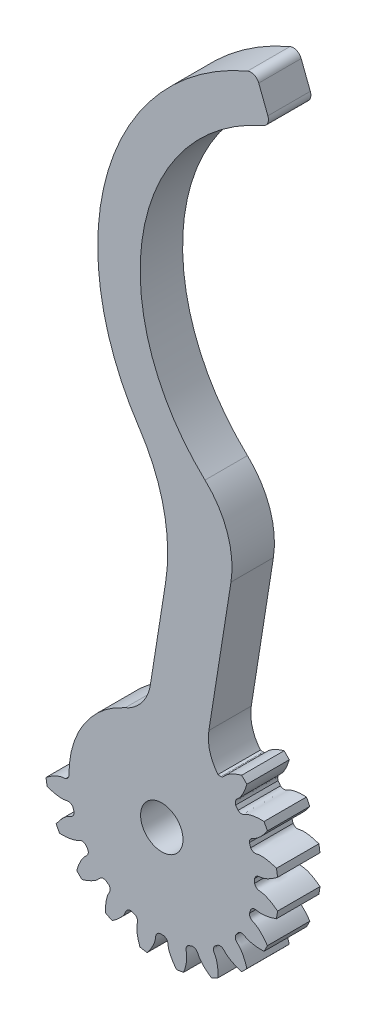
SolidWorks part; units mm, degrees
material "聚脂树脂"
ref_plane "前视基准面" through (0, 0, 0) normal (0, 0, 1) x (1, 0, 0)
ref_plane "上视基准面" through (0, 0, 0) normal (0, 1, 0) x (1, 0, 0)
ref_plane "右视基准面" through (0, 0, 0) normal (1, 0, 0) x (0, 0, -1)
other "Configuration Table"
sketch "草图1" plane through (0, 0, 0) normal (0, 0, 1) x (1, 0, 0)
  circle A0 centre (0, 0) radius 13.75
extrude "凸台-拉伸1" add sketch "草图1" along normal blind 5
ref_axis "基准轴1" through (0, 0, -1.5) along (0, 0, 1)
sketch "草图2" plane through (0, 0, 0) normal (0, 0, 1) x (1, 0, 0)
  line L0 (0, 0) -> (0, 13.75) construction
  circle A0 centre (0, 0) radius 13.75 construction
  arc A1 (0.2416, 10.9348) -> (-0.2416, 10.9348) centre (0, 0) ccw
  arc A2 (3.9764, 15.6228) -> (-3.9764, 15.6228) centre (0, 0) ccw
  spline S0 degree 3 poles (0.2416, 10.9348) (0.764, 11.1168) (0.6964, 11.4839) (0.7661, 11.8375) (0.7736, 11.8719) (0.7829, 11.9108) (0.7941, 11.954) (0.8075, 12.0015) (0.8231, 12.0532) (0.8413, 12.1091) (0.8621, 12.169) (0.8857, 12.2329) (0.9123, 12.3007) (0.9421, 12.3723) (0.9752, 12.4476) (1.0117, 12.5264) (1.0519, 12.6088) (1.0959, 12.6945) (1.1438, 12.7834) (1.1957, 12.8755) (1.2519, 12.9705) (1.3125, 13.0684) (1.3775, 13.1691) (1.4472, 13.2723) (1.5216, 13.3779) (1.601, 13.4858) (1.6853, 13.5958) (1.7747, 13.7078) (1.8694, 13.8216) (1.9693, 13.937) (2.0748, 14.0539) (2.1857, 14.1721) (2.3023, 14.2914) (2.4246, 14.4116) (2.5527, 14.5326) (2.6866, 14.6542) (2.8265, 14.7761) (2.9725, 14.8983) (3.1245, 15.0204) (3.2826, 15.1424) (3.4469, 15.2639) (3.6768, 15.427) (3.8549, 15.5454) (3.9764, 15.6228) knots 0 0 0 0 0.165916 0.170906 0.176664 0.183189 0.190482 0.198542 0.207371 0.216967 0.22733 0.238462 0.250361 0.263027 0.276462 0.290664 0.305634 0.321371 0.337876 0.355149 0.37319 0.391998 0.411574 0.431917 0.453028 0.474907 0.497554 0.520968 0.54515 0.570099 0.595817 0.622302 0.649554 0.677575 0.706363 0.735918 0.766242 0.797333 0.829191 0.861818 0.895212 0.929373 1 1 1 1
  spline S1 degree 3 poles (-0.2416, 10.9348) (-0.764, 11.1168) (-0.6964, 11.4839) (-0.7661, 11.8375) (-0.7736, 11.8719) (-0.7829, 11.9108) (-0.7941, 11.954) (-0.8075, 12.0015) (-0.8231, 12.0532) (-0.8413, 12.1091) (-0.8621, 12.169) (-0.8857, 12.2329) (-0.9123, 12.3007) (-0.9421, 12.3723) (-0.9752, 12.4476) (-1.0117, 12.5264) (-1.0519, 12.6088) (-1.0959, 12.6945) (-1.1438, 12.7834) (-1.1957, 12.8755) (-1.2519, 12.9705) (-1.3125, 13.0684) (-1.3775, 13.1691) (-1.4472, 13.2723) (-1.5216, 13.3779) (-1.601, 13.4858) (-1.6853, 13.5958) (-1.7747, 13.7078) (-1.8694, 13.8216) (-1.9693, 13.937) (-2.0748, 14.0539) (-2.1857, 14.1721) (-2.3023, 14.2914) (-2.4246, 14.4116) (-2.5527, 14.5326) (-2.6866, 14.6542) (-2.8265, 14.7761) (-2.9725, 14.8983) (-3.1245, 15.0204) (-3.2826, 15.1424) (-3.4469, 15.2639) (-3.6768, 15.427) (-3.8549, 15.5454) (-3.9764, 15.6228) knots 0 0 0 0 0.165916 0.170906 0.176664 0.183189 0.190482 0.198542 0.207371 0.216967 0.22733 0.238462 0.250361 0.263027 0.276462 0.290664 0.305634 0.321371 0.337876 0.355149 0.37319 0.391998 0.411574 0.431917 0.453028 0.474907 0.497554 0.520968 0.54515 0.570099 0.595817 0.622302 0.649554 0.677575 0.706363 0.735918 0.766242 0.797333 0.829191 0.861818 0.895212 0.929373 1 1 1 1
extrude "切除-拉伸1" cut sketch "草图2" along normal through all
pattern_circular "阵列(圆周)1" count 20 every 18 about axis through (0, 0, -1.5) along (0, 0, 1) of "切除-拉伸1"
sketch "草图6" plane through (0, 0, 0) normal (0, 0, -1) x (-1, 0, 0)
  line L0 (0, 0) -> (-10.311, 65.1009) construction
  line L1 (0, 0) -> (38.9643, 6.1713) construction
  line L2 (0, 0) -> (-30.4582, -4.8241) construction
  line L3 (-12.3461, -1.9554) -> (-21.1812, 53.827) construction
  line L4 (3.4569, 0.5475) -> (-2.1703, 36.0761)
  line L5 (-3.4569, -0.5475) -> (-9.0841, 34.981)
  line L6 (-9.0841, 34.981) -> (-15.0031, 72.3522)
  line L7 (-15.0031, 72.3522) -> (-21.4537, 55.5478) construction
  line L8 (-15.0031, 72.3522) -> (-7.9754, 90.6601) construction
  line L9 (-15.0031, 72.3522) -> (-11.6329, 81.132)
  line L10 (-3.4569, -0.5475) -> (3.4569, 0.5475)
  line L11 (-11.6329, 81.132) -> (-11.061, 82.6216)
  circle A0 centre (0, 0) radius 12.5 construction
  circle A1 centre (-21.4537, 55.5478) radius 24 construction
  circle A2 centre (-21.4537, 55.5478) radius 27.4044 construction
  arc A3 (-11.6329, 81.132) -> (-2.1703, 36.0761) centre (-21.4537, 55.5478) cw
  arc A4 (-12.8529, 77.9537) -> (-9.0841, 34.981) centre (-21.4537, 55.5478) cw
  circle A5 centre (-21.4537, 55.5478) radius 29
  dimension "D1" = 25
  dimension "D4" = 48
  dimension "D5" = 30
  dimension "D6" = 58
  dimension "D2" = 7
  dimension "D3" = 58.22
extrude "凸台-拉伸2" add sketch "草图6" against normal blind 5 contours A3 L9 L6 L5 L10 L4 | L4 | A5 L5 L10 L4 region at (2.4566, 15.9006, 0) region at (5.2225, 32.179, 0) region at (1.5039, 35.2004, 0)
ref_plane "基准面1" through (12.5, 0, 0) normal (1, 0, 0) x (0, 0, -1)
ref_axis "基准轴2" through (0, 0, -6) along (0, 0, 1)
ref_plane "基准面2" through (0, 0, 0) normal (-0.9877, 0.1564, 0) x (0, 0, 1)
ref_plane "基准面3" through (12.3461, -1.9554, 0) normal (-0.9877, 0.1564, 0) x (0, 0, 1)
sketch "草图16" plane through (0, 0, 5) normal (0, 0, 1) x (1, 0, 0)
  circle A0 centre (0, 0) radius 2.5
  dimension "D1" = 5
extrude "切除-拉伸5" cut sketch "草图16" against normal blind 16.5
sketch "草图20" plane through (0, 0, 0) normal (0, 0, -1) x (-1, 0, 0)
  line L0 (0, 0) -> (3.6089, 10.325)
  line L1 (3.6089, 10.325) -> (7.1451, 20.4421)
  line L2 (0, 0) -> (10.9348, -0.2416)
  line L3 (10.9348, -0.2416) -> (20.7519, -0.2416)
  circle A0 centre (0, 0) radius 17.5
  circle A1 centre (0, 0) radius 10.9375
  arc A2 (-8.7044, 6.6228) -> (-8.9885, 6.2318) centre (0, 0) ccw construction
  dimension "D1" = 35
extrude "切除-拉伸8" cut sketch "草图20" against normal blind 10 contours A1 L3 A0 L1 region at (-11.1082, 7.7459, 0)
fillet "圆角3" radius 10 1 edges at (9.0841, 34.981, 2.5)
fillet "圆角4" radius 1 2 edges at (11.061, 82.6216, 2.5) (12.8529, 77.9537, 2.5)
sketch "草图23" plane through (0, 0, 5) normal (0, 0, 1) x (1, 0, 0)
  line L0 (-1.4427, 13.2649) -> (-5.0779, -9.6873)
  line L1 (1.8671, 34.1617) -> (-1.4427, 13.2649) construction
  line L2 (5.4711, 12.1699) -> (1.8359, -10.7823)
  line L3 (8.1537, 29.1071) -> (5.4711, 12.1699) construction
  circle A0 centre (0, 0) radius 10.9375
  arc A1 (-1.7221, 13.6417) -> (-2.5777, 13.5062) centre (0, 0) ccw construction
  arc A2 (-1.7221, 13.6417) -> (-2.5777, 13.5062) centre (0, 0) ccw
  arc A3 (6.6252, 12.0486) -> (5.8534, 12.4419) centre (0, 0) ccw construction
  arc A4 (6.6252, 12.0486) -> (5.8534, 12.4419) centre (0, 0) ccw
  spline S0 degree 3 poles (996.9007, 66.1041) (-88.8946, -5.2942) (-13.4757, 28.9809) (-1.601, 13.4858) (-1.5216, 13.3779) (7.2871, 0.8786) (-29.1617, -42.7887) (-976.2266, -209.8122) knots -9.021595 -9.021595 -9.021595 -9.021595 0.502446 0.525093 0.546972 0.568083 8.020067 8.020067 8.020067 8.020067 only from (-1.7221, 13.6417) to (-1.4427, 13.2649) construction
  spline S1 degree 3 poles (-1001.8702, -39.9652) (14.2454, 6.0691) (-2.4742, 7.7001) (-2.931, 11.5081) (-2.9354, 11.558) (-2.9398, 11.6323) (-2.9424, 11.7223) (-2.941, 11.8445) (-2.9339, 11.9853) (-2.9194, 12.1444) (-2.8961, 12.3215) (-2.8626, 12.516) (-2.8175, 12.7274) (-2.7593, 12.9551) (-2.6999, 13.1539) (-2.6447, 13.3205) (3.8605, 31.7266) (86.1798, 22.4348) (-968.5361, -245.1905) knots -1.696649 -1.696649 -1.696649 -1.696649 0.165916 0.170906 0.183189 0.190482 0.207371 0.22733 0.250361 0.276462 0.305634 0.337876 0.37319 0.411574 0.453028 0.474907 0.497554 10.021595 10.021595 10.021595 10.021595 only from (-3.1492, 10.4743) to (-2.5777, 13.5062) construction
  spline S2 degree 3 poles (-1.7221, 13.6417) (-1.653, 13.5549) (-1.5584, 13.4302) (-1.4684, 13.3023) (-1.4427, 13.2649) knots 0.492568 0.492568 0.492568 0.492568 0.546972 0.569233 0.569233 0.569233 0.569233
  spline S3 degree 3 poles (-3.1492, 10.4743) (-2.7087, 10.8088) (-2.8864, 11.137) (-2.931, 11.5081) (-2.9354, 11.558) (-2.9398, 11.6323) (-2.9424, 11.7223) (-2.941, 11.8445) (-2.9339, 11.9853) (-2.9194, 12.1444) (-2.8961, 12.3215) (-2.8626, 12.516) (-2.8175, 12.7274) (-2.7593, 12.9551) (-2.6866, 13.1982) (-2.6232, 13.3832) (-2.5848, 13.4873) (-2.5777, 13.5062) knots 0 0 0 0 0.165916 0.170906 0.183189 0.190482 0.207371 0.22733 0.250361 0.276462 0.305634 0.337876 0.37319 0.411574 0.453028 0.497554 0.507432 0.507432 0.507432 0.507432
  spline S4 degree 3 poles (845.3644, -532.484) (-75.0291, 47.9678) (6.1325, 31.3668) (6.6326, 11.8082) (6.6318, 11.5928) (6.6211, 11.3487) (6.6022, 11.1239) (6.5767, 10.9187) (6.5461, 10.7332) (6.5119, 10.5675) (6.4757, 10.4216) (6.4439, 10.3125) (6.4137, 10.2194) (6.3905, 10.1545) (6.3633, 10.0853) (6.3437, 10.0391) (4.7326, 6.5586) (-11.6727, 10.1742) (940.4849, -347.6039) knots -9.021595 -9.021595 -9.021595 -9.021595 0.502446 0.525093 0.568083 0.608002 0.644851 0.678629 0.709336 0.736973 0.761538 0.783033 0.792629 0.809518 0.816811 0.829094 0.834084 2.696649 2.696649 2.696649 2.696649 only from (6.6252, 12.0486) to (6.2318, 8.9885) construction
  spline S5 degree 3 poles (863.6256, -501.2214) (14.5123, -49.7066) (-6.659, 3.0874) (5.5812, 12.2529) (5.6899, 12.331) (21.7717, 23.3982) (82.9074, -32.5047) (-927.6725, 370.9244) knots -7.020109 -7.020109 -7.020109 -7.020109 0.431917 0.453028 0.474907 0.497554 10.021567 10.021567 10.021567 10.021567 only from (5.4711, 12.1699) to (5.8534, 12.4419) construction
  spline S6 degree 3 poles (6.6252, 12.0486) (6.6301, 11.9377) (6.6341, 11.7422) (6.6276, 11.4683) (6.6126, 11.2338) (6.5902, 11.0188) (6.5619, 10.8235) (6.5293, 10.6479) (6.4939, 10.4921) (6.4623, 10.3749) (6.4317, 10.2737) (6.4078, 10.2024) (6.3839, 10.1378) (6.3633, 10.0853) (6.3437, 10.0391) (6.1867, 9.7) (5.9162, 9.4428) (6.2318, 8.9885) knots 0.492568 0.492568 0.492568 0.492568 0.546972 0.588426 0.62681 0.662124 0.694366 0.723538 0.749639 0.77267 0.783033 0.801458 0.809518 0.816811 0.829094 0.834084 1 1 1 1
  spline S7 degree 3 poles (5.4711, 12.1699) (5.5426, 12.2247) (5.6688, 12.3172) (5.798, 12.4053) (5.8534, 12.4419) knots 0.430767 0.430767 0.430767 0.430767 0.474907 0.507432 0.507432 0.507432 0.507432
extrude "切除-拉伸10" cut sketch "草图23" against normal blind 10 contours S3 A0 L0 S2 A2 | S7 L2 A0 S6 A4 region at (-2.2448, 12.1367, 5) region at (5.8854, 10.849, 5)
fillet "圆角7" radius 5 2 edges at (5.0779, 9.6873, 2.5) (-1.8359, 10.7823, 2.5)
fillet "圆角8" radius 20 1 edges at (1.8671, 34.1617, 2.5)
